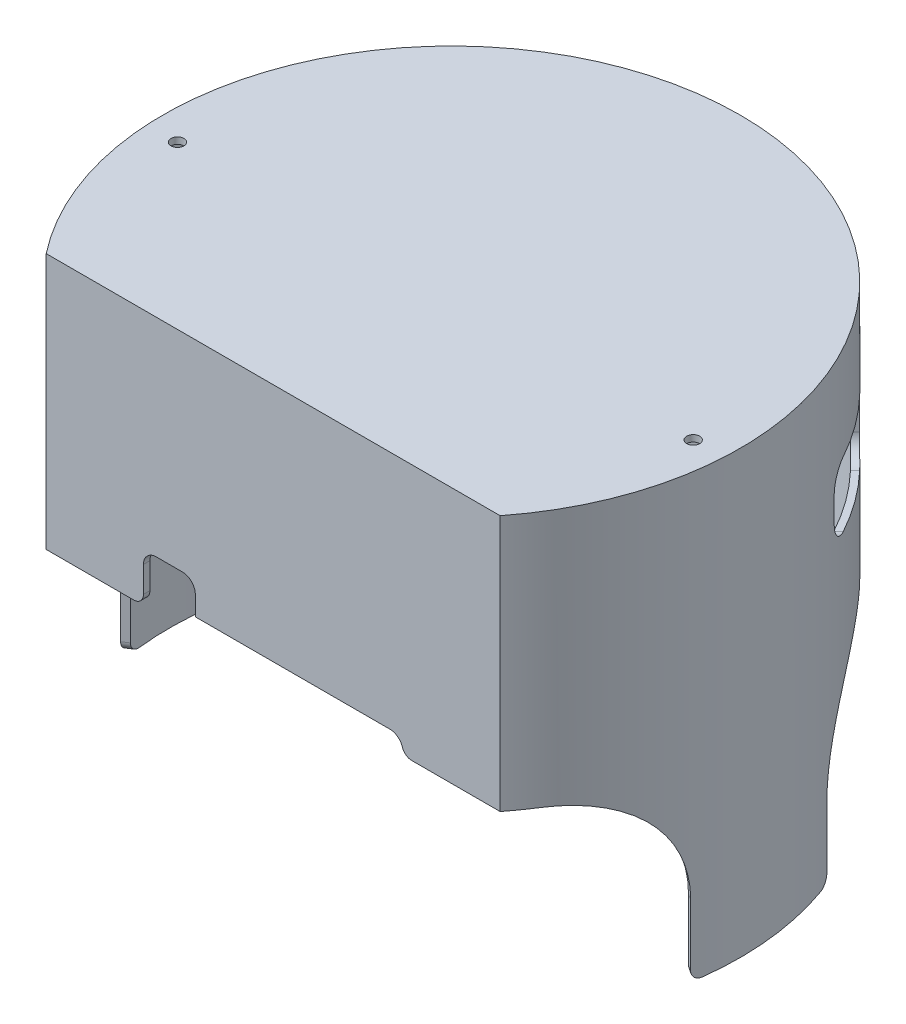
SolidWorks part; units mm, degrees
ref_plane "Front" through (0, 0, 0) normal (0, 0, 1) x (1, 0, 0)
ref_plane "Top" through (0, 0, 0) normal (0, 1, 0) x (1, 0, 0)
ref_plane "Right" through (0, 0, 0) normal (1, 0, 0) x (0, 0, -1)
sketch "Sketch1" plane through (0, 0, 0) normal (0, 1, 0) x (1, 0, 0)
  line L0 (-69.9714, -55) -> (69.9714, -55)
  line L1 (-68.9928, -53) -> (68.9928, -53)
  arc A0 (-69.9714, -55) -> (69.9714, -55) centre (0, 0) cw
  arc A1 (-68.9928, -53) -> (68.9928, -53) centre (0, 0) cw
  dimension "D1" = 89
  dimension "D3" = 87
  dimension "D2" = 55
  dimension "D4" = 53
extrude "Extrude1" add sketch "Sketch1" along normal blind 134
sketch "Sketch5" plane through (0, 134, 0) normal (0, 1, 0) x (1, 0, 0)
  line L0 (-69.9714, -55) -> (69.9714, -55) construction
  line L1 (-69.9714, -55) -> (69.9714, -55)
  arc A0 (69.9714, -55) -> (-69.9714, -55) centre (0, 0) ccw
extrude "Extrude4" add sketch "Sketch5" along normal blind 2
sketch "Sketch6" plane through (0, 0, 55) normal (0, 0, 1) x (1, 0, 0)
  line L0 (-69.9714, 0) -> (69.9714, 0) construction
  line L1 (-40, 0) -> (40, 0)
  line L2 (-40, 0) -> (-40, 62)
  line L3 (-40, 62) -> (40, 62)
  line L4 (40, 0) -> (40, 62)
  dimension "D1" = 40
  dimension "D2" = 40
  dimension "D3" = 62
extrude "Extrude5" cut sketch "Sketch6" against normal blind 5
sketch "Sketch7" plane through (0, 0, 55) normal (0, 0, 1) x (1, 0, 0)
  line L1 (-40, 62) -> (-24, 62)
  line L2 (-40, 62) -> (-40, 72)
  line L3 (-40, 72) -> (-24, 72)
  line L4 (-24, 62) -> (-24, 72)
  dimension "D1" = 10
  dimension "D2" = 16
extrude "Extrude6" cut sketch "Sketch7" against normal blind 5
sketch "Sketch8" plane through (0, 136, 0) normal (0, 1, 0) x (-1, 0, 0)
  circle A0 centre (79.5, 5) radius 2
  circle A1 centre (-79.5, 5) radius 2
  dimension "D1" = 4
  dimension "D3" = 4
  dimension "D5" = 5
  dimension "D2" = 79.5
  dimension "D4" = 79.5
extrude "Extrude7" cut sketch "Sketch8" against normal blind 5
sketch "Sketch9" plane through (0, 0, 55) normal (0, 0, 1) x (1, 0, 0)
  line L0 (-69.9714, 136) -> (-69.9714, 0) construction
  line L1 (-40, 0) -> (-69.9714, 0)
  line L2 (-40, 0) -> (-40, 57)
  line L3 (-40, 57) -> (-69.9714, 57)
  line L4 (-69.9714, 0) -> (-69.9714, 57)
  dimension "D1" = 57
extrude "Extrude8" cut sketch "Sketch9" against normal blind 5
mirror "Mirror1" about plane through (0, 0, 0) normal (1, 0, 0) of "Extrude8"
fillet "Fillet1" radius 4 3 edges at (-40, 72, 54) (-24, 72, 54) (40, 62, 54)
sketch "Sketch12" plane through (0, 0, 0) normal (1, 0, 0) x (0, 0, -1)
  line L0 (0, 136) -> (0, 0)
ref_plane "Plane 45" through (0, 0, 0) normal (0.7071, 0, 0.7071) x (0.7071, 0, -0.7071)
ref_plane "Plane 33" through (0, 0, 0) normal (-0.8387, 0, 0.5446) x (0.5446, 0, 0.8387)
sketch "Sketch13" plane through (0, 0, 0) normal (-0.8387, 0, 0.5446) x (0.5446, 0, 0.8387)
  line L1 (8.0177, 0) -> (-35.9823, 0)
  line L2 (8.0177, 0) -> (8.0177, 57)
  line L3 (8.0177, 57) -> (-35.9823, 57)
  line L4 (-35.9823, 0) -> (-35.9823, 57)
  dimension "D1" = 57
  dimension "D2" = 44
extrude "Extrude16" cut sketch "Sketch13" along normal blind 100
fillet "Fillet4" radius 35 1 edges at (-86.9477, 57, 13.5606)
sketch "Sketch14" plane through (0, 0, 0) normal (0.7071, 0, 0.7071) x (0.7071, 0, -0.7071)
  line L0 (-72.142, 0) -> (89, 0) construction
  line L1 (-35, 0) -> (35, 0)
  line L2 (-35, 0) -> (-35, 57)
  line L3 (-35, 57) -> (35, 57)
  line L4 (35, 0) -> (35, 57)
  dimension "D1" = 57
  dimension "D2" = 70
  dimension "D3" = 35
extrude "Extrude17" cut sketch "Sketch14" against normal blind 100
fillet "Fillet5" radius 35 2 edges at (-32.3425, 57, -81.8399) (-81.8399, 57, -32.3425)
mirror "Mirror3" about plane through (0, 0, 0) normal (1, 0, 0) of "Fillet5", "Extrude17", "Fillet4", "Extrude16"
fillet "Fillet6" radius 3 9 edges at (0, 134, -87) (32.3425, 0, -81.8399) (81.8399, 0, -32.3425) (86.9477, 0, 13.5606) (40, 57, 54) (-40, 57, 54) (-32.3425, 0, -81.8399) (-81.8399, 0, -32.3425) (-86.9477, 0, 13.5606)
ref_plane "Plane6" through (0, 0, 0) normal (-0.7071, 0, 0.7071) x (0.7071, 0, 0.7071)
sketch "Sketch16" plane through (0, 0, 0) normal (-0.7071, 0, 0.7071) x (0.7071, 0, 0.7071)
  line L0 (88.3681, 136) -> (-89, 136) construction
  line L1 (31, 107) -> (-4, 107)
  line L2 (31, 107) -> (31, 87)
  line L3 (31, 87) -> (-4, 87)
  line L4 (-4, 107) -> (-4, 87)
  line L5 (-89, 136) -> (-89, 57) construction
  dimension "D1" = 35
  dimension "D2" = 20
  dimension "D3" = 29
  dimension "D4" = 85
extrude "Extrude19" cut sketch "Sketch16" against normal blind 100
fillet "Fillet7" radius 6 4 edges at (80.1563, 107, -36.3157) (59.3326, 107, -64.9895) (80.1563, 87, -36.3157) (59.3326, 87, -64.9895)
sketch "Sketch17" plane through (0, 0, 0) normal (0, 0, 1) x (1, 0, 0)
  line L0 (89, 136) -> (-89, 136) construction
  line L1 (53, 108) -> (22.5, 108)
  line L2 (53, 108) -> (53, 93)
  line L3 (53, 93) -> (22.5, 93)
  line L4 (22.5, 108) -> (22.5, 93)
  line L6 (-22.5, 108) -> (-53, 108)
  line L7 (-22.5, 108) -> (-22.5, 93)
  line L8 (-22.5, 93) -> (-53, 93)
  line L9 (-53, 108) -> (-53, 93)
  dimension "D1" = 53
  dimension "D2" = 15
  dimension "D3" = 28
  dimension "D4" = 22.5
  dimension "D5" = 53
  dimension "D6" = 15
  dimension "D7" = 22.5
extrude "Extrude20" cut sketch "Sketch17" against normal blind 100
fillet "Fillet8" radius 5 8 edges at (53, 108, -70.2455) (53, 93, -70.2455) (22.5, 108, -85.0746) (22.5, 93, -85.0746) (-22.5, 108, -85.0746) (-22.5, 93, -85.0746) (-53, 93, -70.2455) (-53, 108, -70.2455)
sketch "Sketch19" plane through (0, 0, 55) normal (0, 0, 1) x (1, 0, 0)
  text T0 "IMMORTALS" font "Segoe Print" height in points 36
extrude "Extrude21" [suppressed] cut sketch "Sketch19" against normal up to surface (2 mm away)
